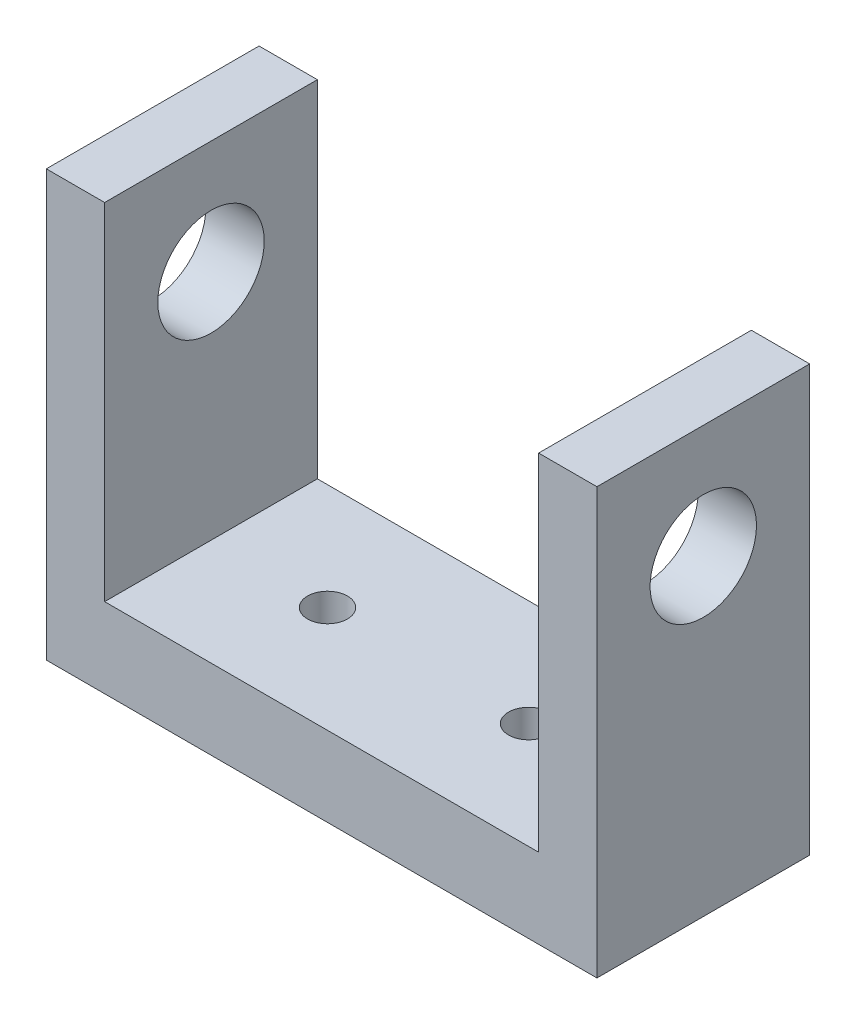
SolidWorks part; units mm, degrees
ref_plane "Front Plane" through (0, 0, 0) normal (0, 0, 1) x (1, 0, 0)
ref_plane "Top Plane" through (0, 0, 0) normal (0, 1, 0) x (1, 0, 0)
ref_plane "Right Plane" through (0, 0, 0) normal (1, 0, 0) x (0, 0, -1)
sketch "Sketch1" plane through (0, 0, 0) normal (0, 1, 0) x (1, 0, 0)
  line L1 (-8.2176, -3.175) -> (8.2176, -3.175)
  line L2 (-8.2176, -3.175) -> (-8.2176, 3.175)
  line L3 (-8.2176, 3.175) -> (8.2176, 3.175)
  line L4 (8.2176, -3.175) -> (8.2176, 3.175)
  line L5 (-8.2176, -3.175) -> (8.2176, 3.175) construction
  line L6 (-8.2176, 3.175) -> (8.2176, -3.175) construction
  point P0 (0, 0)
  dimension "D1" = 16.4353
  dimension "D2" = 6.35
extrude "Boss-Extrude1" add sketch "Sketch1" along normal blind 12.7
sketch "Sketch2" plane through (0, 12.7, 0) normal (0, 1, 0) x (-1, 0, 0)
  line L0 (-8.2176, -3.175) -> (8.2176, -3.175) construction
  line L1 (6.477, 3.175) -> (-6.477, 3.175)
  line L2 (6.477, 3.175) -> (6.477, -3.175)
  line L3 (6.477, -3.175) -> (-6.477, -3.175)
  line L4 (-6.477, 3.175) -> (-6.477, -3.175)
  line L5 (6.477, 3.175) -> (-6.477, -3.175) construction
  line L6 (6.477, -3.175) -> (-6.477, 3.175) construction
  point P0 (0, 0)
  dimension "D1" = 12.954
extrude "Cut-Extrude1" cut sketch "Sketch2" against normal offset from surface (10.3187 mm away) 2.3813 up to face at (0, 0, 0)
sketch "Sketch3" plane through (8.2176, 0, 0) normal (1, 0, 0) x (0, 0, -1)
  line L0 (-3.175, 0) -> (3.175, 0) construction
  circle A0 centre (0, 9.3218) radius 1.5875
  dimension "D1" = 3.175
  dimension "D2" = 9.3218
extrude "Cut-Extrude2" cut sketch "Sketch3" against normal through all
hole_wizard "#0-80 Tapped Hole1" positions "Sketch5" profile "Sketch4" tap size "#0-80" standard "Ansi Inch" end condition through all
sketch "Sketch5" plane through (0, 2.3813, 0) normal (0, 1, 0) x (-1, 0, 0)
  point P1 (3, 0)
  point P3 (-3, 0)
  dimension "D1" = 3
  dimension "D2" = 3
sketch "Sketch4" plane through (-3, 2.3813, 0) normal (1, 0, 0) x (0, 0, 1)
  line L0 (0, 0) -> (0, 2.3813)
  line L1 (0, 2.3813) -> (0.5956, 2.3813)
  line L2 (0.5956, 2.3813) -> (0.5956, 0)
  line L5 (0.5956, 0) -> (0, 0)
  line L11 (0, -6.35) -> (0, 107.95) construction
  dimension "Thread Major Dia." = 1.1913
  dimension "Thru Tap Drill Depth" = 2.3813
